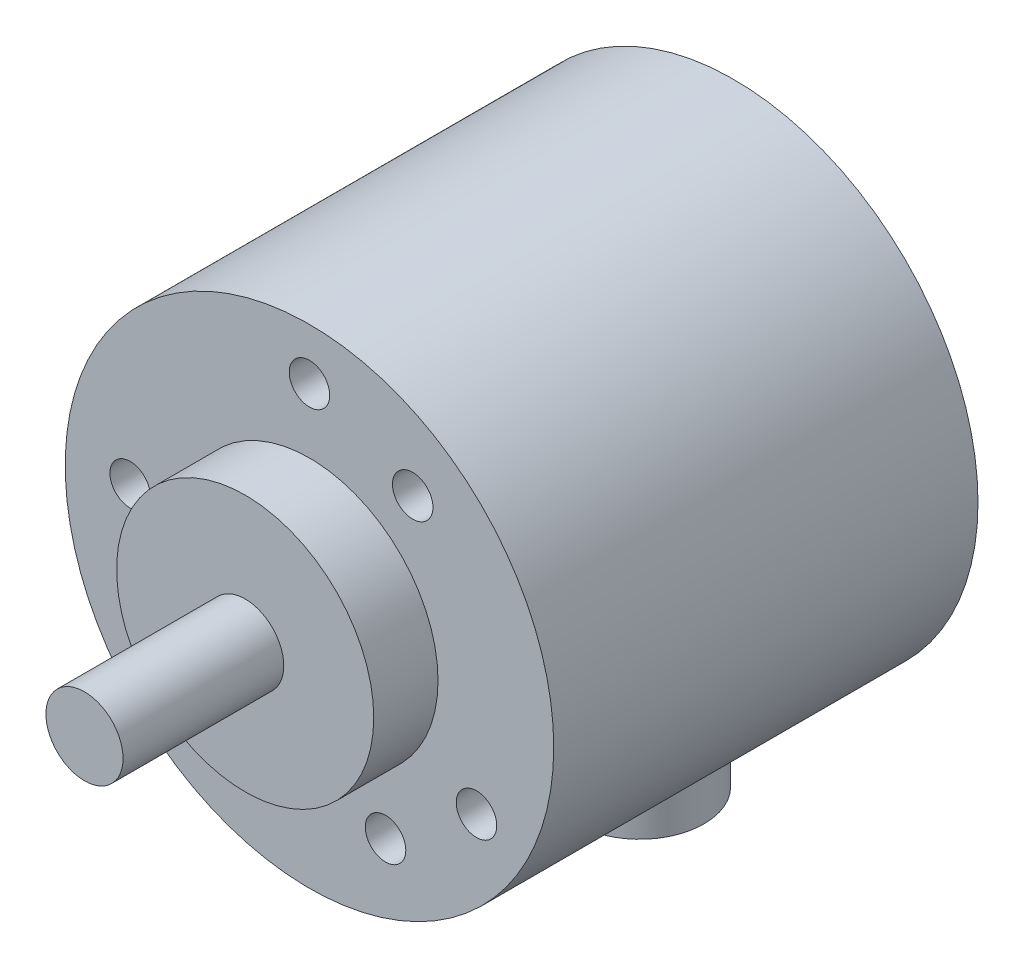
SolidWorks part; units mm, degrees
ref_plane "Front Plane" through (0, 0, 0) normal (0, 0, 1) x (1, 0, 0)
ref_plane "Top Plane" through (0, 0, 0) normal (0, 1, 0) x (1, 0, 0)
ref_plane "Right Plane" through (0, 0, 0) normal (1, 0, 0) x (0, 0, -1)
sketch "Sketch2" plane through (0, 0, 0) normal (0, 0, 1) x (1, 0, 0)
  circle A0 centre (0, 0) radius 19
  circle A1 centre (0, 0) radius 3
  circle A2 centre (0, 0) radius 10
  dimension "D1" = 38
  dimension "D2" = 6
  dimension "D3" = 20
extrude "Boss-Extrude1" add sketch "Sketch2" against normal blind 33 contours A0 A2 | A2 A1 | A1 region at (-18.4626, 0, 0) region at (0, 0, 0) region at (-9.7172, 0, 0)
extrude "Boss-Extrude2" add sketch "Sketch2<3>" along normal blind 5 contours A2 A1 region at (-9.7172, 0, 0)
sketch "Sketch2<3>" plane through (0, 0, 0) normal (0, 0, 1) x (1, 0, 0) same geometry as "Sketch2"
extrude "Boss-Extrude3" add sketch "Sketch2<4>" along normal blind 17.5 contours A1 region at (0, 0, 0)
sketch "Sketch2<4>" plane through (0, 0, 0) normal (0, 0, 1) x (1, 0, 0) same geometry as "Sketch2"
sketch "Sketch4" plane through (0, 0, 0) normal (0, 1, 0) x (1, 0, 0)
  circle A0 centre (0, 25.6886) radius 5
  dimension "D1" = 10
extrude "Boss-Extrude4" add sketch "Sketch4" against normal blind 25
sketch "Sketch5" plane through (0, 0, 0) normal (0, 0, 1) x (1, 0, 0)
  line L0 (0, 0) -> (0, 27.0968) construction
  line L1 (0, 0) -> (14.9724, 21.3829) construction
  circle A0 centre (0, 0) radius 14 construction
  circle A1 centre (0, 0) radius 15 construction
  circle A2 centre (0, 15) radius 1.575
  circle A5 centre (12.9904, -7.5) radius 1.575
  circle A6 centre (-12.9904, -7.5) radius 1.575
  circle A7 centre (8.0301, 11.4681) radius 1.575
  circle A8 centre (5.9167, -12.6883) radius 1.575
  circle A9 centre (-13.9467, 1.2202) radius 1.575
  point P6 (8.0301, 11.4681)
  point P14 (0, 0)
  point P22 (0, 0)
  dimension "D1" = 28
  dimension "D2" = 30
  dimension "D3" = 3.15
  dimension "D6" = 3.15
  dimension "D7" = 3
  dimension "D4" = 35
  dimension "D5" = 3
extrude "Cut-Extrude1" cut sketch "Sketch5" against normal blind 6
sketch "Sketch6" plane through (0, 0, -33) normal (0, 0, -1) x (-1, 0, 0)
  point P0 (0, 0)
